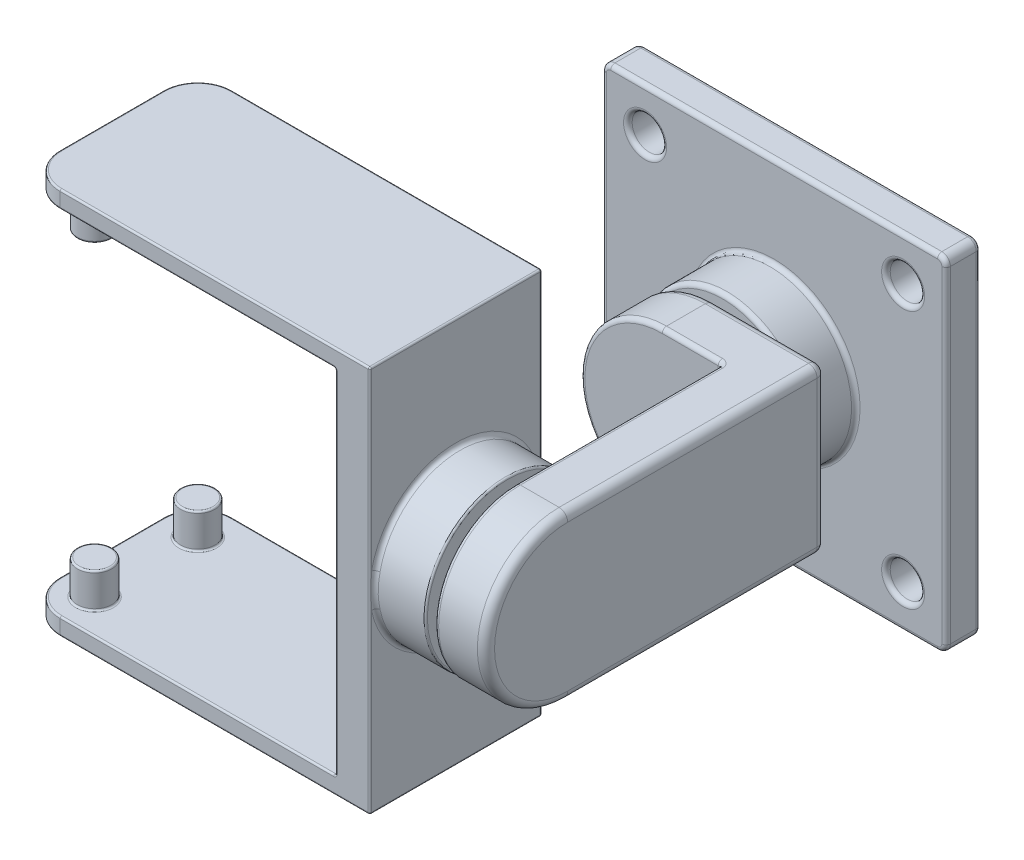
SolidWorks part; units mm, degrees
material "1060 Alloy"
ref_plane "Front Plane" through (0, 0, 0) normal (0, 0, 1) x (1, 0, 0)
ref_plane "Top Plane" through (0, 0, 0) normal (0, 1, 0) x (1, 0, 0)
ref_plane "Right Plane" through (0, 0, 0) normal (1, 0, 0) x (0, 0, -1)
sketch "Sketch1" plane through (0, 0, 0) normal (0, 0, 1) x (1, 0, 0)
  line L0 (0, -10.25) -> (0, 10.25)
  line L1 (0, 10.25) -> (-18, 10.25)
  line L2 (-18, 10.25) -> (-18, 11.25)
  line L3 (-18, 11.25) -> (2, 11.25)
  line L4 (2, 11.25) -> (2, -11.25)
  line L5 (2, -11.25) -> (-18, -11.25)
  line L6 (-18, -11.25) -> (-18, -10.25)
  line L7 (-18, -10.25) -> (0, -10.25)
  point P4 (0, 0)
  dimension "D1" = 20.5
  dimension "D2" = 1
  dimension "D3" = 2
  dimension "D4" = 18
extrude "Boss-Extrude1" add sketch "Sketch1" along normal blind 10
sketch "Sketch2" plane through (0, 0, 0) normal (0, 1, 0) x (1, 0, 0)
  line L0 (2, -5) -> (-18, -5) construction
  line L1 (2, -10) -> (2, 0) construction
  line L2 (-18, -10) -> (-18, 0) construction
  circle A0 centre (-16, -2) radius 1
  circle A1 centre (-16, -8) radius 1
  dimension "D1" = 2
  dimension "D2" = 2
  dimension "D3" = 6
extrude "Boss-Extrude2" add sketch "Sketch2" along normal blind 2 from surface starting at face at (-9, -10.25, 5)
extrude "Boss-Extrude3" add sketch "Sketch2<2>" against normal blind 2 from surface starting at face at (-9, 10.25, 5)
sketch "Sketch2<2>" plane through (0, 0, 0) normal (0, 1, 0) x (1, 0, 0) same geometry as "Sketch2"
fillet "Fillet1" radius 2 4 edges at (-18, -10.75, 10) (-18, 10.75, 10) (-18, 10.75, 0) (-18, -10.75, 0)
fillet "Fillet2" radius 0.1 36 edges at (0, 0, 0) (0, 0, 10) (0, 10.25, 5) (-8, 10.25, 0) (-17.4142, 10.25, 0.5858) (-18, 10.25, 5) (-17.4142, 10.25, 9.4142) (-8, 10.25, 10) (-17, 10.25, 2) (-17, 10.25, 8) (-17.4142, -10.25, 0.5858) (-8, -10.25, 0) (0, -10.25, 5) (-8, -10.25, 10) (-17.4142, -10.25, 9.4142) (-18, -10.25, 5) (-16, -10.25, 1) (-16, -10.25, 7) (2, 0, 10) (2, 0, 0) (2, -11.25, 5) (-7, -11.25, 0) (-17.4142, -11.25, 0.5858) (-18, -11.25, 5) (-17.4142, -11.25, 9.4142) (-7, -11.25, 10) (-17.4142, 11.25, 0.5858) (-7, 11.25, 0) (2, 11.25, 5) (-7, 11.25, 10) (-17.4142, 11.25, 9.4142) (-18, 11.25, 5) (-17, 8.25, 2) (-17, 8.25, 8) (-16, -8.25, 1) (-16, -8.25, 7)
sketch "Sketch4" plane through (2, 0, 0) normal (1, 0, 0) x (0, 0, -1)
  line L0 (-5, 11.15) -> (-5, -11.15) construction
  line L1 (-0.1, 11.15) -> (-9.9, 11.15) construction
  line L2 (-9.9, -11.15) -> (-0.1, -11.15) construction
  circle A0 centre (-5, 0) radius 4.75
  dimension "D1" = 9.5
extrude "Boss-Extrude4" add sketch "Sketch4" along normal blind 3
fillet "Fillet3" radius 0.1 1 edges at (5, 4.75, 5)
sketch "Sketch5" plane through (5, 0, 0) normal (1, 0, 0) x (0, 0, -1)
  circle A0 centre (-5, 0) radius 3
  dimension "D1" = 6
extrude "Boss-Extrude5" add sketch "Sketch5" along normal blind 0.5
sketch "Sketch6" plane through (5.5, 0, 0) normal (1, 0, 0) x (0, 0, -1)
  circle A0 centre (-5, 0) radius 4.75 construction
  circle A1 centre (-5, 0) radius 4.75
extrude "Boss-Extrude6" add sketch "Sketch6" along normal blind 3
sketch "Sketch7" plane through (8.5, 0, 0) normal (1, 0, 0) x (0, 0, -1)
  line L1 (-5, 4.75) -> (10, 4.75)
  line L2 (-5, 4.75) -> (-5, -4.75)
  line L3 (-5, -4.75) -> (10, -4.75)
  line L4 (10, 4.75) -> (10, -4.75)
  circle A0 centre (-5, 0) radius 4.75 construction
  circle A1 centre (-5, 0) radius 4.75 construction
  dimension "D1" = 15
  dimension "D2" = 9.5
extrude "Boss-Extrude7" add sketch "Sketch7" against normal up to surface (3 mm away) up to face at (5.5, 3, 5)
sketch "Sketch9" plane through (0, 0, -10) normal (0, 0, -1) x (-1, 0, 0)
  line L1 (-2, 4.75) -> (-2, -4.75) construction
  line L2 (-8.5, 4.75) -> (-2, 4.75)
  line L3 (-8.5, 4.75) -> (-8.5, -4.75)
  line L4 (-8.5, -4.75) -> (-2, -4.75)
  arc A0 (-2, -4.75) -> (-2, 4.75) centre (-2, 0) ccw
  dimension "D1" = 9.5
extrude "Boss-Extrude8" add sketch "Sketch9" against normal blind 3
sketch "Sketch10" plane through (0, 0, -10) normal (0, 0, -1) x (-1, 0, 0)
  circle A0 centre (-2, 0) radius 3
  dimension "D1" = 6
extrude "Boss-Extrude9" add sketch "Sketch10" along normal blind 0.5
sketch "Sketch11" plane through (0, 0, -10.5) normal (0, 0, -1) x (-1, 0, 0)
  circle A0 centre (-2, 0) radius 4.75
  arc A1 (-2, -4.75) -> (-2, 4.75) centre (-2, 0) ccw construction
extrude "Boss-Extrude10" add sketch "Sketch11" along normal blind 3
sketch "Sketch12" plane through (0, 0, -13.5) normal (0, 0, -1) x (-1, 0, 0)
  line L1 (-12, 10) -> (8, 10)
  line L2 (-12, 10) -> (-12, -10)
  line L3 (-12, -10) -> (8, -10)
  line L4 (8, 10) -> (8, -10)
  line L5 (-2, -10) -> (-2, 10) construction
  line L6 (-12, 0) -> (8, 0) construction
  point P0 (-2, 0)
  dimension "D1" = 20
  dimension "D2" = 20
extrude "Boss-Extrude11" add sketch "Sketch12" along normal blind 2
fillet "Fillet4" radius 0.5 4 edges at (12, -10, -14.5) (-8, -10, -14.5) (12, 10, -14.5) (-8, 10, -14.5)
sketch "Sketch13" plane through (0, 0, -15.5) normal (0, 0, -1) x (-1, 0, 0)
  line L0 (-2, 10) -> (-2, -10) construction
  line L1 (7.5, 10) -> (-11.5, 10) construction
  line L2 (-11.5, -10) -> (7.5, -10) construction
  line L3 (-12, 0) -> (8, 0) construction
  line L4 (-12, 9.5) -> (-12, -9.5) construction
  line L5 (8, -9.5) -> (8, 9.5) construction
  circle A0 centre (5.5, 7.5) radius 1
  circle A1 centre (-9.5, 7.5) radius 1
  circle A2 centre (-9.5, -7.5) radius 1
  circle A3 centre (5.5, -7.5) radius 1
  dimension "D1" = 2
  dimension "D2" = 7.5
  dimension "D3" = 2.5
  dimension "D4" = 15
  dimension "D5" = 15
extrude "Cut-Extrude1" cut sketch "Sketch13" against normal up to next
fillet "Fillet5" radius 0.5 7 edges at (5.25, -4.75, -10) (-2.75, 0, -10) (8.5, 4.75, -2.5) (8.5, -4.75, -2.5) (8.5, 0, -10) (5.25, 4.75, -10) (8.5, 0, 9.75)
fillet "Fillet6" radius 0.25 34 edges at (5.5, 4.75, -1) (5.5, -4.75, -1) (11.8536, 9.8536, -15.5) (2, 10, -15.5) (-7.8536, 9.8536, -15.5) (-8, 0, -15.5) (-7.8536, -9.8536, -15.5) (2, -10, -15.5) (11.8536, -9.8536, -15.5) (12, 0, -15.5) (-6.5, 7.5, -15.5) (8.5, -7.5, -15.5) (10.5, 7.5, -15.5) (-4.5, -7.5, -15.5) (-7.8536, -9.8536, -13.5) (-8, 0, -13.5) (-7.8536, 9.8536, -13.5) (2, 10, -13.5) (11.8536, 9.8536, -13.5) (12, 0, -13.5) (11.8536, -9.8536, -13.5) (2, -10, -13.5) (-6.5, 7.5, -13.5) (8.5, -7.5, -13.5) (8.5, 7.5, -13.5) (-6.5, -7.5, -13.5) (-2.75, 0, -10.5) (-2.75, 0, -13.5) (-2.75, 0, -7) (3.75, 4.75, -7) (5.5, 0, -7) (3.75, -4.75, -7) (2, -4.75, 5) (5.5, 0, 9.75)
